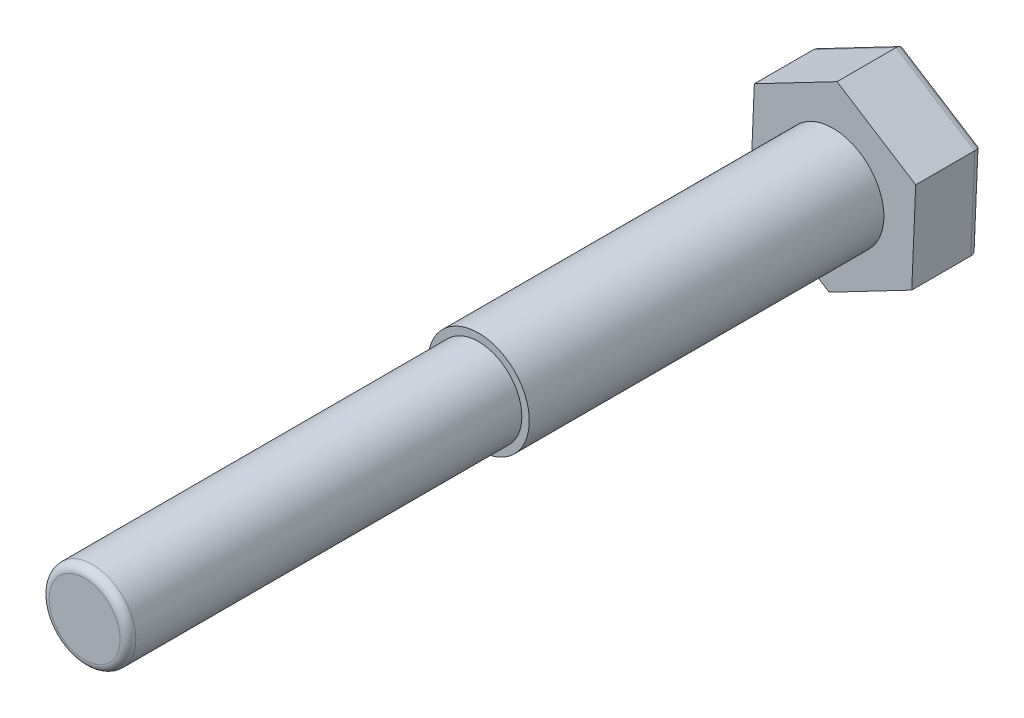
SolidWorks part; units mm, degrees
ref_plane "前视" through (0, 0, 0) normal (0, 0, 1) x (1, 0, 0)
ref_plane "上视" through (0, 0, 0) normal (0, 1, 0) x (1, 0, 0)
ref_plane "右视" through (0, 0, 0) normal (1, 0, 0) x (0, 0, -1)
sketch "草图1" plane through (0, 0, 0) normal (0, 0, 1) x (1, 0, 0)
  line L1 (20.9842, 10.9543) -> (1.0054, 23.65)
  line L2 (1.0054, 23.65) -> (-19.9788, 12.6957)
  line L3 (-19.9788, 12.6957) -> (-20.9842, -10.9543)
  line L4 (-20.9842, -10.9543) -> (-1.0054, -23.65)
  line L5 (-1.0054, -23.65) -> (19.9788, -12.6957)
  line L6 (19.9788, -12.6957) -> (20.9842, 10.9543)
  circle A0 centre (0, 0) radius 20.5 construction
  dimension "D1" = 47.3
  dimension "D2" = 41
extrude "基体-拉伸" add sketch "草图1" along normal blind 17
sketch "草图2" plane through (0, 0, 17) normal (0, 0, 1) x (1, 0, 0)
  circle A0 centre (0, 0) radius 12.9
  dimension "D1" = 25.8
extrude "凸台-拉伸1" add sketch "草图2" along normal blind 90
fillet "圆角3" radius 2 6 edges at (10.9948, 17.3021, 0) (-9.4867, 18.1729, 0) (-20.4815, 0.8707, 0) (-10.9948, -17.3021, 0) (9.4867, -18.1729, 0) (20.4815, -0.8707, 0)
sketch "草图3" plane through (0, 0, 107) normal (0, 0, 1) x (1, 0, 0)
  circle A0 centre (0, 0) radius 11
  dimension "D1" = 22
extrude "凸台-拉伸2" add sketch "草图3" along normal blind 100
fillet "圆角4" radius 2 1 edges at (11, 0, 207)
